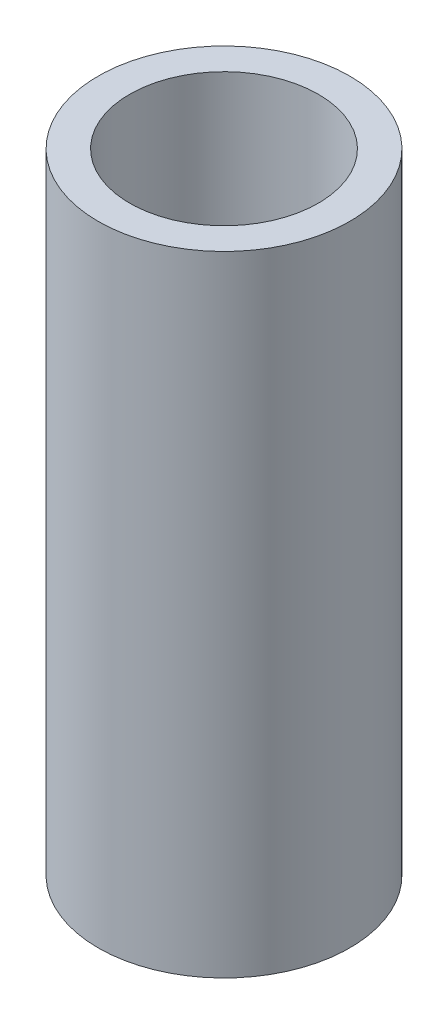
SolidWorks part; units mm, degrees
ref_plane "Спереди" through (0, 0, 0) normal (0, 0, 1) x (1, 0, 0)
ref_plane "Сверху" through (0, 0, 0) normal (0, 1, 0) x (1, 0, 0)
ref_plane "Справа" through (0, 0, 0) normal (1, 0, 0) x (0, 0, -1)
sketch "Эскиз1" plane through (0, 0, 0) normal (0, 1, 0) x (1, 0, 0)
  circle A0 centre (0, 0) radius 20
extrude "Вытянуть-Тонкостенный1" add sketch "Эскиз1" along normal blind 100 thin thin type one direction reverse wall 5
